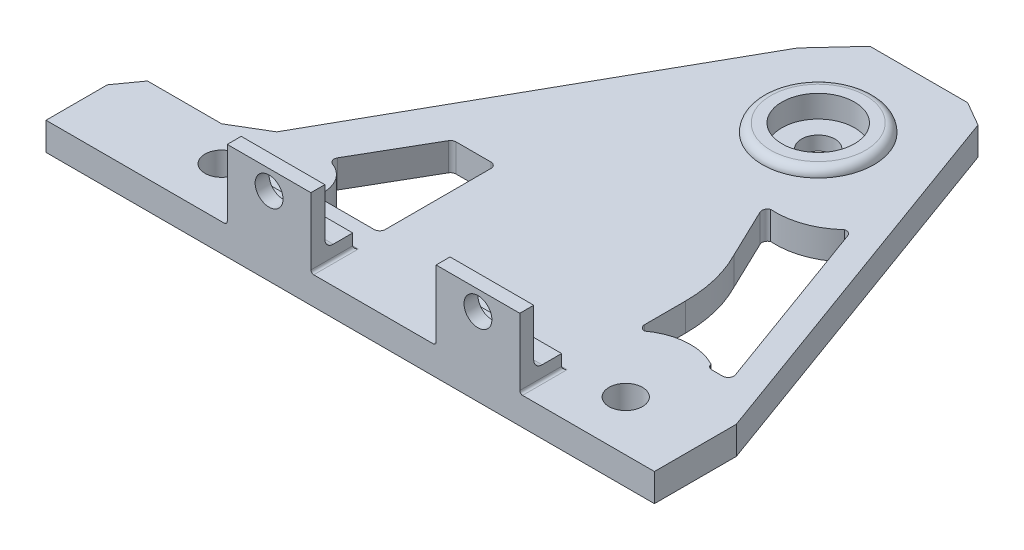
SolidWorks part; units mm, degrees
ref_plane "Alzado" through (0, 0, 0) normal (0, 0, 1) x (1, 0, 0)
ref_plane "Planta" through (0, 0, 0) normal (0, 1, 0) x (1, 0, 0)
ref_plane "Vista lateral" through (0, 0, 0) normal (1, 0, 0) x (0, 0, -1)
sketch "Croquis1" plane through (0, 0, 0) normal (0, 1, 0) x (1, 0, 0)
  line L0 (-109.095, 0) -> (109.095, 0)
  line L1 (-109.095, 0) -> (-109.095, 22)
  line L2 (-109.095, 22) -> (-103.085, 30.39)
  line L3 (-103.085, 30.39) -> (-76.4898, 30.39)
  line L4 (-76.4898, 30.39) -> (-64.095, 37.77)
  line L5 (-64.095, 37.77) -> (3.225, 157.21)
  line L6 (3.225, 157.21) -> (15.6978, 170.7122)
  line L7 (15.6978, 170.7122) -> (50.6978, 170.7122)
  line L8 (50.6978, 170.7122) -> (59.5004, 165.63)
  line L9 (59.5004, 165.63) -> (109.095, 29.37)
  line L10 (109.095, 29.37) -> (109.095, 0)
  line L11 (-34.9592, 24.9055) -> (-16.3292, 24.9055)
  line L12 (-14.3292, 26.9055) -> (-14.3292, 64.8055)
  line L13 (-16.3292, 66.8055) -> (-28.8645, 66.8055)
  line L14 (-30.5966, 65.8055) -> (-45.1245, 40.6425)
  line L15 (-36.9592, 26.9055) -> (-36.9592, 27.4711)
  line L16 (70.5188, 107.9281) -> (93.5924, 44.534)
  line L17 (91.713, 41.85) -> (87.8539, 41.85)
  line L24 (61.7193, 43.85) -> (61.7193, 58.5)
  line L26 (56.1328, 81.4661) -> (47.4697, 99.5151)
  circle A0 centre (33.1978, 134.63) radius 13
  circle A1 centre (33.1978, 134.63) radius 6
  circle A4 centre (-64.095, 18) radius 6
  circle A5 centre (80.805, 18) radius 6
  arc A11 (-36.9592, 27.4711) -> (-44.095, 37.77) centre (-47.9592, 27.4711) ccw
  arc A12 (-16.3292, 24.9055) -> (-14.3292, 26.9055) centre (-16.3292, 26.9055) ccw
  arc A13 (-34.9592, 24.9055) -> (-36.9592, 26.9055) centre (-34.9592, 26.9055) cw
  arc A14 (-44.095, 37.77) -> (-45.1245, 40.6425) centre (-43.3924, 39.6425) cw
  arc A15 (-14.3292, 64.8055) -> (-16.3292, 66.8055) centre (-16.3292, 64.8055) ccw
  arc A16 (-30.5966, 65.8055) -> (-28.8645, 66.8055) centre (-28.8645, 64.8055) cw
  arc A20 (91.713, 41.85) -> (93.5924, 44.534) centre (91.713, 43.85) ccw
  arc A22 (61.7193, 58.5) -> (56.1328, 81.4661) centre (11.7193, 58.5) ccw
  arc A24 (87.8539, 41.85) -> (85.8794, 43.5319) centre (87.8539, 43.85) cw
  arc A25 (63.7193, 41.85) -> (61.7193, 43.85) centre (63.7193, 43.85) cw
  arc A26 (70.5188, 107.9281) -> (68.0232, 109.1468) centre (68.6395, 107.2441) ccw
  arc A29 (63.7193, 41.85) -> (85.8794, 43.5319) centre (76.1479, 24.9228) cw
  arc A31 (47.4697, 99.5151) -> (48.5533, 102.2467) centre (49.2727, 100.3805) cw
  arc A32 (48.5533, 102.2467) -> (68.0232, 109.1468) centre (50.3012, 128.2338) ccw
  point P4 (0, 0)
  point P16 (33.1978, 170.7122)
  point P41 (-14.3292, 24.9055)
  point P44 (-36.9592, 24.9055)
  point P47 (-46.4391, 38.3655)
  point P50 (-14.3292, 66.8055)
  point P53 (-30.0192, 66.8055)
  point P65 (61.7193, 58.4)
  point P66 (94.5693, 41.85)
  point P68 (46.5352, 101.462)
  point P74 (61.7193, 41.85)
  point P77 (69.0251, 112.0322)
  point P80 (45.1703, 104.3057)
  dimension "D17" = 26
  dimension "D18" = 12
  dimension "D25" = 12
  dimension "D26" = 12
  dimension "D37" = 60
  dimension "D40" = 11
  dimension "D44" = 2
  dimension "D45" = 50
  dimension "D49" = 16.65
  dimension "D48" = 2
  dimension "D52" = 14.65
  dimension "D54" = 2
  dimension "D55" = 21
  dimension "D57" = 26.0458
  dimension "D59" = 107.9281
  dimension "D60" = 109.1468
  dimension "D62" = 43.5319
  dimension "D64" = 14.4286
  dimension "D46" = 2
  dimension "D68" = 33.9178
  dimension "D69" = 31.9503
  dimension "D70" = 31.9653
  dimension "D1" = 218.19
  dimension "D2" = 22
  dimension "D3" = 6.01
  dimension "D4" = 30.39
  dimension "D5" = 37.77
  dimension "D6" = 30.77
  dimension "D7" = 157.21
  dimension "D8" = 132.731
  dimension "D9" = 150
  dimension "D10" = 112.32
  dimension "D11" = 35
  dimension "D12" = 29.37
  dimension "D13" = 165.63
  dimension "D14" = 110
  dimension "D15" = 45
  dimension "D16" = 134.63
  dimension "D19" = 36.0822
  dimension "D22" = 45
  dimension "D23" = 18
  dimension "D24" = 28.29
  dimension "D38" = 22.63
  dimension "D39" = 15.69
  dimension "D41" = 41.9
  dimension "D42" = 28.44
  dimension "D43" = 65
  dimension "D47" = 32.85
  dimension "D50" = 71.83
  dimension "D51" = 41.85
  dimension "D53" = 24.84
  dimension "D56" = 5.64
  dimension "D58" = 22.18
  dimension "D61" = 12.0653
  dimension "D63" = 16.9719
  dimension "D65" = 23.0999
  dimension "D66" = 5.64
  dimension "D67" = 5.64
extrude "Saliente-Extruir1" add sketch "Croquis1" along normal blind 10 contours L10 L9 L8 L7 L6 L5 L4 L3 L2 L1 L0 A29 A25 L24 A22 L26 A26 L16 A20 L17 A24 A5 A4 A0 L14 A16 L13 A15 L12 A12 L11 A13 L15 A11 region at (15.9565, 0, -64.4741)
sketch "Croquis2" plane through (0, 10, 0) normal (0, 1, 0) x (1, 0, 0)
  line L0 (-109.095, 0) -> (109.095, 0) construction
  line L1 (-44.095, 15) -> (-14.095, 15)
  line L2 (-44.095, 15) -> (-44.095, 0)
  line L3 (-44.095, 0) -> (-14.095, 0)
  line L4 (-14.095, 15) -> (-14.095, 0)
  line L5 (-44.095, 15) -> (-14.095, 0) construction
  line L6 (-44.095, 0) -> (-14.095, 15) construction
  line L7 (30.805, 15) -> (60.805, 15)
  line L8 (30.805, 15) -> (30.805, 0)
  line L9 (30.805, 0) -> (60.805, 0)
  line L10 (60.805, 15) -> (60.805, 0)
  line L11 (30.805, 15) -> (60.805, 0) construction
  line L12 (30.805, 0) -> (60.805, 15) construction
  line L13 (-109.095, 0) -> (-109.095, 22) construction
  point P0 (-29.095, 7.5)
  point P5 (45.805, 7.5)
  dimension "D1" = 15
  dimension "D2" = 0
  dimension "D3" = 0
  dimension "D4" = 15
  dimension "D5" = 65
  dimension "D6" = 30
  dimension "D7" = 30
  dimension "D8" = 48.29
extrude "Saliente-Extruir2" add sketch "Croquis2" along normal blind 5
ref_plane "Plano1" through (0, 15, 0) normal (0, 1, 0) x (1, 0, 0)
sketch "Croquis3" plane through (0, 15, 0) normal (0, 1, 0) x (1, 0, 0)
  line L0 (-44.095, 15) -> (-44.095, 0) construction
  line L1 (-44.095, 5) -> (-14.095, 5)
  line L2 (-44.095, 5) -> (-44.095, 0)
  line L3 (-44.095, 0) -> (-14.095, 0)
  line L4 (-14.095, 5) -> (-14.095, 0)
  line L5 (-44.095, 0) -> (-14.095, 0) construction
  line L6 (30.805, 15) -> (30.805, 0) construction
  line L7 (30.805, 5) -> (60.805, 5)
  line L8 (30.805, 5) -> (30.805, 0)
  line L9 (30.805, 0) -> (60.805, 0)
  line L10 (60.805, 5) -> (60.805, 0)
  line L11 (30.805, 0) -> (60.805, 0) construction
  line L13 (109.095, 29.37) -> (109.095, 0) construction
  dimension "D1" = 5
  dimension "D2" = 5
  dimension "D3" = 48.29
  dimension "D4" = 123.19
extrude "Saliente-Extruir3" add sketch "Croquis3" along normal blind 20
ref_plane "Plano2" through (0, 0, -5) normal (0, 0, -1) x (-1, 0, 0)
sketch "Croquis4" plane through (0, 0, -5) normal (0, 0, -1) x (-1, 0, 0)
  line L0 (-30.805, 35) -> (-30.805, 15) construction
  line L1 (44.095, 35) -> (44.095, 15) construction
  line L2 (-60.805, 35) -> (-30.805, 35) construction
  line L3 (14.095, 35) -> (44.095, 35) construction
  circle A0 centre (-45.805, 28) radius 5
  circle A1 centre (29.095, 28) radius 5
  dimension "D1" = 10
  dimension "D2" = 10
  dimension "D3" = 15
  dimension "D4" = 15
  dimension "D5" = 7
  dimension "D6" = 7
extrude "Cortar-Extruir1" cut sketch "Croquis4" against normal blind 20
fillet "Redondeo1" radius 1 4 edges at (60.805, 10, -7.5) (-14.095, 10, -7.5) (30.805, 10, -7.5) (-44.095, 10, -7.5)
fillet "Redondeo2" radius 1 2 edges at (45.805, 10, -15) (-29.095, 10, -15)
fillet "Redondeo3" radius 3 2 edges at (45.805, 15, -5) (-29.095, 15, -5)
sketch "Croquis5" plane through (0, 0, 0) normal (0, -1, 0) x (1, 0, 0)
  circle A0 centre (33.1978, -134.63) radius 13
  circle A1 centre (33.1978, -134.63) radius 6
  dimension "D1" = 26
  dimension "D2" = 12
extrude "Saliente-Extruir4" add sketch "Croquis5" against normal blind 5
sketch "Croquis6" plane through (0, 10, 0) normal (0, 1, 0) x (1, 0, 0)
  circle A0 centre (33.1978, 134.63) radius 20
  circle A1 centre (33.1978, 134.63) radius 13
  dimension "D1" = 40
  dimension "D2" = 26
extrude "Saliente-Extruir5" add sketch "Croquis6" along normal blind 3
fillet "Redondeo4" radius 3 1 edges at (33.1978, 13, -114.63)
